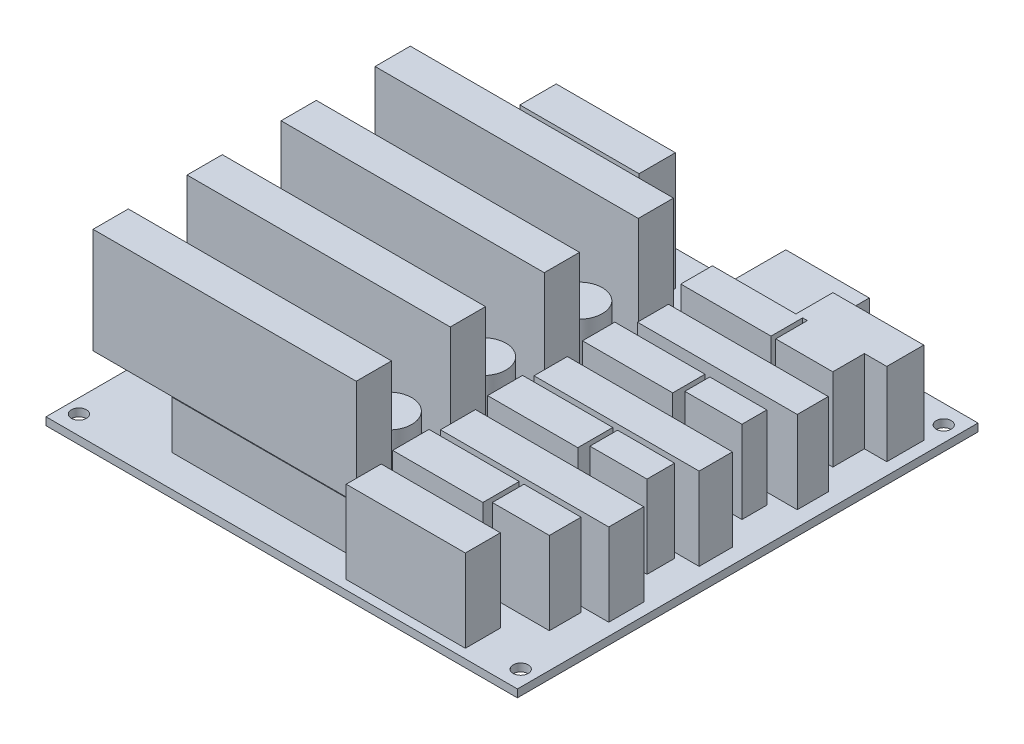
SolidWorks part; units mm, degrees
ref_plane "Front Plane" through (0, 0, 0) normal (0, 0, 1) x (1, 0, 0)
ref_plane "Top Plane" through (0, 0, 0) normal (0, 1, 0) x (1, 0, 0)
ref_plane "Right Plane" through (0, 0, 0) normal (1, 0, 0) x (0, 0, -1)
sketch "Sketch2" plane through (0, 0, 0) normal (0, 1, 0) x (1, 0, 0)
  line L0 (-37.5547, 13.8096) -> (18.4453, 13.8096)
  line L1 (-50.15, -49) -> (50.15, -49)
  line L2 (-50.15, -49) -> (-50.15, 49)
  line L3 (-50.15, 49) -> (50.15, 49)
  line L4 (50.15, -49) -> (50.15, 49)
  line L5 (-50.15, -49) -> (50.15, 49) construction
  line L6 (-50.15, 49) -> (50.15, -49) construction
  line L7 (-37.5547, 38.8096) -> (18.4453, 38.8096)
  line L8 (-37.5547, 38.8096) -> (-37.5547, 31.3096)
  line L9 (-37.5547, 31.3096) -> (18.4453, 31.3096)
  line L10 (18.4453, 38.8096) -> (18.4453, 31.3096)
  line L11 (-37.5547, 38.8096) -> (18.4453, 31.3096) construction
  line L12 (-37.5547, 31.3096) -> (18.4453, 38.8096) construction
  line L13 (-37.5547, 13.8096) -> (-37.5547, 6.3096)
  line L14 (-37.5547, 6.3096) -> (18.4453, 6.3096)
  line L15 (18.4453, 13.8096) -> (18.4453, 6.3096)
  line L16 (-37.5547, 13.8096) -> (18.4453, 6.3096) construction
  line L17 (-37.5547, 6.3096) -> (18.4453, 13.8096) construction
  line L18 (-37.5547, -11.1904) -> (18.4453, -11.1904)
  line L19 (-37.5547, -11.1904) -> (-37.5547, -18.6904)
  line L20 (-37.5547, -18.6904) -> (18.4453, -18.6904)
  line L21 (18.4453, -11.1904) -> (18.4453, -18.6904)
  line L22 (-37.5547, -11.1904) -> (18.4453, -18.6904) construction
  line L23 (-37.5547, -18.6904) -> (18.4453, -11.1904) construction
  line L24 (-37.5547, -36.1904) -> (18.4453, -36.1904)
  line L25 (-37.5547, -36.1904) -> (-37.5547, -43.6904)
  line L26 (-37.5547, -43.6904) -> (18.4453, -43.6904)
  line L27 (18.4453, -36.1904) -> (18.4453, -43.6904)
  line L28 (-37.5547, -36.1904) -> (18.4453, -43.6904) construction
  line L29 (-37.5547, -43.6904) -> (18.4453, -36.1904) construction
  line L30 (-9.5547, 35.0596) -> (-9.5547, 10.0596) construction
  circle A0 centre (-15.345, -29) radius 6
  circle A1 centre (-0.345, -29) radius 6
  circle A2 centre (-15.345, -4) radius 6
  circle A3 centre (-0.345, -4) radius 6
  circle A4 centre (-15.345, 21) radius 6
  circle A5 centre (-0.345, 21) radius 6
  point P0 (0, 0)
  point P22 (-9.5547, 35.0596)
  point P28 (-9.5547, 10.0596)
  point P33 (-9.5547, -14.9404)
  point P38 (-9.5547, -39.9404)
  dimension "D3" = 15
  dimension "D4" = 12
  dimension "D1" = 100.3
  dimension "D2" = 98
  dimension "D5" = 25
  dimension "D6" = 25
  dimension "D7" = 20
  dimension "D8" = 4
  dimension "D9" = 25
  dimension "D10" = 7.5
  dimension "D11" = 56
extrude "Boss-Extrude1" add sketch "Sketch2" along normal blind 1.65 contours L10 L7 L8 L9 | L15 L0 L13 L14 | L21 L18 L19 L20 | L27 L24 L25 L26 | A0 | A1 | A2 | A3 | A4 | A5 | L1 L4 L3 L2 A5 A4 A3 A2 A1 A0 L7 L10 L9 L8 L0 L15 L14 L13 L18 L21 L20 L19 L24 L27 L26 L25 region at (-9.5547, 0, -10.0596) region at (-48.7477, 0, 0) region at (-9.5547, 0, -35.0596) region at (-9.5547, 0, 14.9404) region at (-9.5547, 0, 39.9404) region at (-15.345, 0, 29) region at (-0.345, 0, 29) region at (-15.345, 0, 4) region at (-0.345, 0, 4) region at (-15.345, 0, -21) region at (-0.345, 0, -21)
sketch "Sketch5" plane through (0, 1.65, 0) normal (0, 1, 0) x (1, 0, 0)
  line L0 (395.1903, -42.3334) -> (395.1903, -505.6667) construction
  line L2 (-50.15, 49) -> (50.15, 49)
  line L3 (-50.15, 49) -> (-50.15, -49)
  line L4 (-50.15, -49) -> (50.15, -49)
  line L5 (50.15, 49) -> (50.15, -49)
  line L6 (-50.15, 49) -> (50.15, -49) construction
  line L7 (-50.15, -49) -> (50.15, 49) construction
  line L8 (-30.1953, -34.8724) -> (8.9074, -34.8724)
  line L9 (-30.1953, -34.8724) -> (-30.1953, -42.1773)
  line L10 (-30.1953, -42.1773) -> (8.9074, -42.1773)
  line L11 (8.9074, -34.8724) -> (8.9074, -42.1773)
  line L12 (-30.1953, -34.8724) -> (8.9074, -42.1773) construction
  line L13 (-30.1953, -42.1773) -> (8.9074, -34.8724) construction
  line L14 (-30.1953, -14.1036) -> (8.9074, -14.1036)
  line L15 (-30.1953, -14.1036) -> (-30.1953, -21.9814)
  line L16 (-30.1953, -21.9814) -> (8.9074, -21.9814)
  line L17 (8.9074, -14.1036) -> (8.9074, -21.9814)
  line L18 (-30.1953, -14.1036) -> (8.9074, -21.9814) construction
  line L19 (-30.1953, -21.9814) -> (8.9074, -14.1036) construction
  line L20 (-30.1953, 6.0923) -> (8.9074, 6.0923)
  line L21 (-30.1953, 6.0923) -> (-30.1953, -2.072)
  line L22 (-30.1953, -2.072) -> (8.9074, -2.072)
  line L23 (8.9074, 6.0923) -> (8.9074, -2.072)
  line L24 (-30.1953, 6.0923) -> (8.9074, -2.072) construction
  line L25 (-30.1953, -2.072) -> (8.9074, 6.0923) construction
  line L26 (-30.1953, 25.4288) -> (8.9074, 25.4288)
  line L27 (-30.1953, 25.4288) -> (-30.1953, 17.9807)
  line L28 (-30.1953, 17.9807) -> (8.9074, 17.9807)
  line L29 (8.9074, 25.4288) -> (8.9074, 17.9807)
  line L30 (-30.1953, 25.4288) -> (8.9074, 17.9807) construction
  line L31 (-30.1953, 17.9807) -> (8.9074, 25.4288) construction
  line L32 (-32.2006, 41.6142) -> (-6.8483, 41.6142)
  line L33 (-32.2006, 41.6142) -> (-32.2006, 33.8796)
  line L34 (-32.2006, 33.8796) -> (-6.8483, 33.8796)
  line L35 (-6.8483, 41.6142) -> (-6.8483, 33.8796)
  line L36 (-32.2006, 41.6142) -> (-6.8483, 33.8796) construction
  line L37 (-32.2006, 33.8796) -> (-6.8483, 41.6142) construction
  line L38 (11.7721, -39.5991) -> (37.1243, -39.5991)
  line L39 (11.7721, -39.5991) -> (11.7721, -47.0472)
  line L40 (11.7721, -47.0472) -> (37.1243, -47.0472)
  line L41 (37.1243, -39.5991) -> (37.1243, -47.0472)
  line L42 (11.7721, -39.5991) -> (37.1243, -47.0472) construction
  line L43 (11.7721, -47.0472) -> (37.1243, -39.5991) construction
  line L44 (10.483, -28.1404) -> (29.6762, -28.1404)
  line L45 (10.483, -28.1404) -> (10.483, -35.875)
  line L46 (10.483, -35.875) -> (29.6762, -35.875)
  line L47 (29.6762, -28.1404) -> (29.6762, -35.875)
  line L48 (10.483, -28.1404) -> (29.6762, -35.875) construction
  line L49 (10.483, -35.875) -> (29.6762, -28.1404) construction
  line L50 (11.7721, -19.5464) -> (37.1243, -19.5464)
  line L51 (11.7721, -19.5464) -> (11.7721, -26.9946)
  line L52 (11.7721, -26.9946) -> (37.1243, -26.9946)
  line L53 (37.1243, -19.5464) -> (37.1243, -26.9946)
  line L54 (11.7721, -19.5464) -> (37.1243, -26.9946) construction
  line L55 (11.7721, -26.9946) -> (37.1243, -19.5464) construction
  line L56 (11.7721, 0) -> (37.1243, 0)
  line L57 (11.7721, 0) -> (11.7721, -7.0851)
  line L58 (11.7721, -7.0851) -> (37.1243, -7.0851)
  line L59 (37.1243, 0) -> (37.1243, -7.0851)
  line L60 (11.7721, 0) -> (37.1243, -7.0851) construction
  line L61 (11.7721, -7.0851) -> (37.1243, 0) construction
  line L62 (10.483, 11.3919) -> (29.6762, 11.3919)
  line L63 (10.483, 11.3919) -> (10.483, 4.5167)
  line L64 (10.483, 4.5167) -> (29.6762, 4.5167)
  line L65 (29.6762, 11.3919) -> (29.6762, 4.5167)
  line L66 (10.483, 11.3919) -> (29.6762, 4.5167) construction
  line L67 (10.483, 4.5167) -> (29.6762, 11.3919) construction
  line L68 (10.483, 32.1608) -> (29.6762, 32.1608)
  line L69 (10.483, 32.1608) -> (10.483, 25.4288)
  line L70 (10.483, 25.4288) -> (29.6762, 25.4288)
  line L71 (29.6762, 32.1608) -> (29.6762, 25.4288)
  line L72 (10.483, 32.1608) -> (29.6762, 25.4288) construction
  line L73 (10.483, 25.4288) -> (29.6762, 32.1608) construction
  line L74 (12.899, 20.3918) -> (36.9021, 20.3918)
  line L75 (12.899, 20.3918) -> (12.899, 13.7908)
  line L76 (12.899, 13.7908) -> (36.9021, 13.7908)
  line L77 (36.9021, 20.3918) -> (36.9021, 13.7908)
  line L78 (12.899, 20.3918) -> (36.9021, 13.7908) construction
  line L79 (12.899, 13.7908) -> (36.9021, 20.3918) construction
  line L80 (28.2439, 40.0386) -> (47.5804, 40.0386)
  line L81 (28.2439, 40.0386) -> (28.2439, 32.1608)
  line L82 (28.2439, 32.1608) -> (47.5804, 32.1608)
  line L83 (47.5804, 40.0386) -> (47.5804, 32.1608)
  line L84 (28.2439, 40.0386) -> (47.5804, 32.1608) construction
  line L85 (28.2439, 32.1608) -> (47.5804, 40.0386) construction
  line L86 (10.483, 47.7732) -> (28.2439, 47.7732)
  line L87 (10.483, 47.7732) -> (10.483, 33.8796)
  line L88 (10.483, 33.8796) -> (28.2439, 33.8796)
  line L89 (28.2439, 47.7732) -> (28.2439, 33.8796)
  line L90 (10.483, 47.7732) -> (28.2439, 33.8796) construction
  line L91 (10.483, 33.8796) -> (28.2439, 47.7732) construction
  line L92 (10.483, -8.231) -> (29.6762, -8.231)
  line L93 (10.483, -8.231) -> (10.483, -15.6791)
  line L94 (10.483, -15.6791) -> (29.6762, -15.6791)
  line L95 (29.6762, -8.231) -> (29.6762, -15.6791)
  line L96 (10.483, -8.231) -> (29.6762, -15.6791) construction
  line L97 (10.483, -15.6791) -> (29.6762, -8.231) construction
  line L98 (30.6874, 11.3919) -> (42.8255, 11.3919)
  line L99 (30.6874, 11.3919) -> (30.6874, 6.0923)
  line L100 (30.6874, 6.0923) -> (42.8255, 6.0923)
  line L101 (42.8255, 11.3919) -> (42.8255, 6.0923)
  line L102 (30.6874, 11.3919) -> (42.8255, 6.0923) construction
  line L103 (30.6874, 6.0923) -> (42.8255, 11.3919) construction
  line L104 (30.6874, -8.231) -> (42.8255, -8.231)
  line L105 (30.6874, -8.231) -> (30.6874, -14.1036)
  line L106 (30.6874, -14.1036) -> (42.8255, -14.1036)
  line L107 (42.8255, -8.231) -> (42.8255, -14.1036)
  line L108 (30.6874, -8.231) -> (42.8255, -14.1036) construction
  line L109 (30.6874, -14.1036) -> (42.8255, -8.231) construction
  line L110 (30.6874, -28.1404) -> (42.8255, -28.1404)
  line L111 (30.6874, -28.1404) -> (30.6874, -34.8724)
  line L112 (30.6874, -34.8724) -> (42.8255, -34.8724)
  line L113 (42.8255, -28.1404) -> (42.8255, -34.8724)
  line L114 (30.6874, -28.1404) -> (42.8255, -34.8724) construction
  line L115 (30.6874, -34.8724) -> (42.8255, -28.1404) construction
  line L116 (37.1243, -19.5464) -> (47.5804, -19.5464)
  line L117 (37.1243, -19.5464) -> (37.1243, -26.9946)
  line L118 (37.1243, -26.9946) -> (47.5804, -26.9946)
  line L119 (47.5804, -19.5464) -> (47.5804, -26.9946)
  line L120 (37.1243, -19.5464) -> (47.5804, -26.9946) construction
  line L121 (37.1243, -26.9946) -> (47.5804, -19.5464) construction
  line L122 (37.1243, 0) -> (46.9038, 0)
  line L123 (37.1243, 0) -> (37.1243, -7.0851)
  line L124 (37.1243, -7.0851) -> (46.9038, -7.0851)
  line L125 (46.9038, 0) -> (46.9038, -7.0851)
  line L126 (37.1243, 0) -> (46.9038, -7.0851) construction
  line L127 (37.1243, -7.0851) -> (46.9038, 0) construction
  line L128 (36.9021, 20.3918) -> (46.9038, 20.3918)
  line L129 (36.9021, 20.3918) -> (36.9021, 13.7908)
  line L130 (36.9021, 13.7908) -> (46.9038, 13.7908)
  line L131 (46.9038, 20.3918) -> (46.9038, 13.7908)
  line L132 (36.9021, 20.3918) -> (46.9038, 13.7908) construction
  line L133 (36.9021, 13.7908) -> (46.9038, 20.3918) construction
  line L134 (30.6874, 32.1608) -> (42.8255, 32.1608)
  line L135 (30.6874, 32.1608) -> (30.6874, 25.4288)
  line L136 (30.6874, 25.4288) -> (42.8255, 25.4288)
  line L137 (42.8255, 32.1608) -> (42.8255, 25.4288)
  line L138 (30.6874, 32.1608) -> (42.8255, 25.4288) construction
  line L139 (30.6874, 25.4288) -> (42.8255, 32.1608) construction
  circle A0 centre (-7.9941, 11.3919) radius 4.9327
  circle A1 centre (2.8916, 11.3919) radius 4.9327
  circle A2 centre (2.7484, 11.5352) radius 4.9327
  circle A3 centre (-7.9941, -9.0904) radius 4.9327
  circle A4 centre (2.8916, -9.0904) radius 4.9327
  circle A5 centre (-7.9941, -29.1431) radius 4.9327
  circle A6 centre (2.8916, -29.1431) radius 4.9327
  point P6 (0, 0)
  point P27 (-10.6439, -38.5248)
  point P32 (-10.6439, -18.0425)
  point P37 (-10.6439, 2.0102)
  point P42 (-10.6439, 21.7047)
  point P47 (-19.5244, 37.7469)
  point P52 (24.4482, -43.3232)
  point P57 (20.0796, -32.0077)
  point P62 (24.4482, -23.2705)
  point P67 (24.4482, -3.5426)
  point P72 (20.0796, 7.9543)
  point P77 (20.0796, 28.7948)
  point P82 (24.9005, 17.0913)
  point P87 (37.9121, 36.0997)
  point P92 (19.3634, 40.8264)
  point P97 (20.0796, -11.9551)
  point P102 (36.7564, 8.7421)
  point P107 (36.7564, -11.1673)
  point P112 (36.7564, -31.5064)
  point P116 (42.3524, -23.2705)
  point P120 (42.0141, -3.5426)
  point P124 (41.903, 17.0913)
  point P128 (36.7564, 28.7948)
extrude "Boss-Extrude4" add sketch "Sketch5" along normal blind 10.2 contours L29 L26 L27 L28 | L23 L20 L21 L22 | L17 L14 L15 L16 | L11 L8 L9 L10 region at (-10.6439, 1.65, 38.5248) region at (-10.6439, 1.65, 18.0425) region at (-10.6439, 1.65, -2.0102) region at (-10.6439, 1.65, -21.7047)
extrude "Boss-Extrude5" add sketch "Sketch5<3>" along normal blind 17.65 contours A1 A2 | A3 | A4 | A6 | A5 | A0 region at (2.82, 1.65, -11.4636) region at (-7.9941, 1.65, 9.0904) region at (2.8916, 1.65, 9.0904) region at (-7.9941, 1.65, 29.1431) region at (2.8916, 1.65, 29.1431)
sketch "Sketch5<3>" plane through (0, 1.65, 0) normal (0, 1, 0) x (1, 0, 0) same geometry as "Sketch5"
hole_wizard "M3 Clearance Hole1" positions "Sketch4" profile "Sketch3" hole size "M3" standard "DIN" end condition through all
sketch "Sketch4" plane through (0, 1.65, 0) normal (0, 1, 0) x (1, 0, 0)
  line L0 (50.15, -49) -> (50.15, 49) construction
  line L1 (-50.15, -49) -> (50.15, -49) construction
  line L2 (-50.15, 49) -> (50.15, 49) construction
  line L3 (-50.15, -49) -> (-50.15, 49) construction
  point P0 (46.85, -45)
  point P2 (46.85, 45)
  point P4 (-47.15, 45)
  point P6 (-47.15, -45)
  dimension "D1" = 3.3
  dimension "D2" = 4
  dimension "D3" = 4
  dimension "D4" = 3.3
  dimension "D5" = 3
  dimension "D6" = 4
  dimension "D7" = 3
  dimension "D8" = 4
sketch "Sketch3" plane through (46.85, 1.65, 45) normal (1, 0, 0) x (0, 0, 1)
  line L0 (0, 0) -> (0, 1.65)
  line L1 (0, 1.65) -> (1.6, 1.65)
  line L2 (1.6, 1.65) -> (1.6, 0)
  line L5 (1.6, 0) -> (0, 0)
  line L11 (0, -6.35) -> (0, 107.95) construction
  dimension "Thru Hole Dia." = 3.2
  dimension "Thru Hole Depth" = 1.65
sketch "Sketch6" plane through (0, 11.85, 0) normal (0, 1, 0) x (1, 0, 0)
  line L0 (-30.1953, 21.7047) -> (-19.0926, 21.7047) construction
  line L1 (-47.0926, 25.4547) -> (8.9074, 25.4547)
  line L2 (-47.0926, 25.4547) -> (-47.0926, 17.9547)
  line L3 (-47.0926, 17.9547) -> (8.9074, 17.9547)
  line L4 (8.9074, 25.4547) -> (8.9074, 17.9547)
  line L5 (-47.0926, 25.4547) -> (8.9074, 17.9547) construction
  line L6 (-47.0926, 17.9547) -> (8.9074, 25.4547) construction
  line L7 (-30.1953, 25.4288) -> (-30.1953, 17.9807) construction
  line L8 (8.9074, 25.4288) -> (8.9074, 17.9807) construction
  point P4 (-19.0926, 21.7047)
  dimension "D1" = 56
  dimension "D2" = 7.5
extrude "Boss-Extrude6" add sketch "Sketch6" along normal blind 22.4
pattern_linear "LPattern1" count 4 spacing 20 along (0, 0, 1) of "Boss-Extrude6"
extrude "Boss-Extrude11" add sketch "Sketch5<4>" along normal blind 17.56 contours L47 L44 L45 L46 | L113 L110 L111 L112 | L53 L50 L51 L52 | L95 L92 L93 L94 | L107 L104 L105 L106 | L59 L56 L57 L58 | L65 L62 L63 L64 | L101 L98 L99 L100 | L71 L68 L69 L70 | L137 L82 L135 L136 | L125 L122 L59 L124 | L119 L116 L53 L118 | L77 L74 L75 L76 | L83 L80 L81 L68 L82 | L131 L128 L77 L130 | L38 L41 L40 L39 region at (20.0796, 1.65, 32.0077) region at (24.4482, 1.65, 23.2705) region at (42.3524, 1.65, 23.2705) region at (24.4482, 1.65, 3.5426) region at (42.0141, 1.65, 3.5426) region at (20.0796, 1.65, -7.9543) region at (20.0796, 1.65, -28.7948) region at (37.9121, 1.65, -36.0997) region at (36.7564, 1.65, -28.7948) region at (24.9005, 1.65, -17.0913) region at (41.903, 1.65, -17.0913) region at (20.0796, 1.65, 11.9551) region at (36.7564, 1.65, -8.7421) region at (36.7564, 1.65, 11.1673) region at (36.7564, 1.65, 31.5064)
sketch "Sketch5<4>" plane through (0, 1.65, 0) normal (0, 1, 0) x (1, 0, 0) same geometry as "Sketch5"
extrude "Boss-Extrude13" add sketch "Sketch5<6>" along normal blind 12.7 contours L87 L88 L89 L86
sketch "Sketch5<6>" plane through (0, 1.65, 0) normal (0, 1, 0) x (1, 0, 0) same geometry as "Sketch5"
extrude "Boss-Extrude14" add sketch "Sketch5<7>" along normal blind 25 contours L32 L35 L34 L33
sketch "Sketch5<7>" plane through (0, 1.65, 0) normal (0, 1, 0) x (1, 0, 0) same geometry as "Sketch5"
